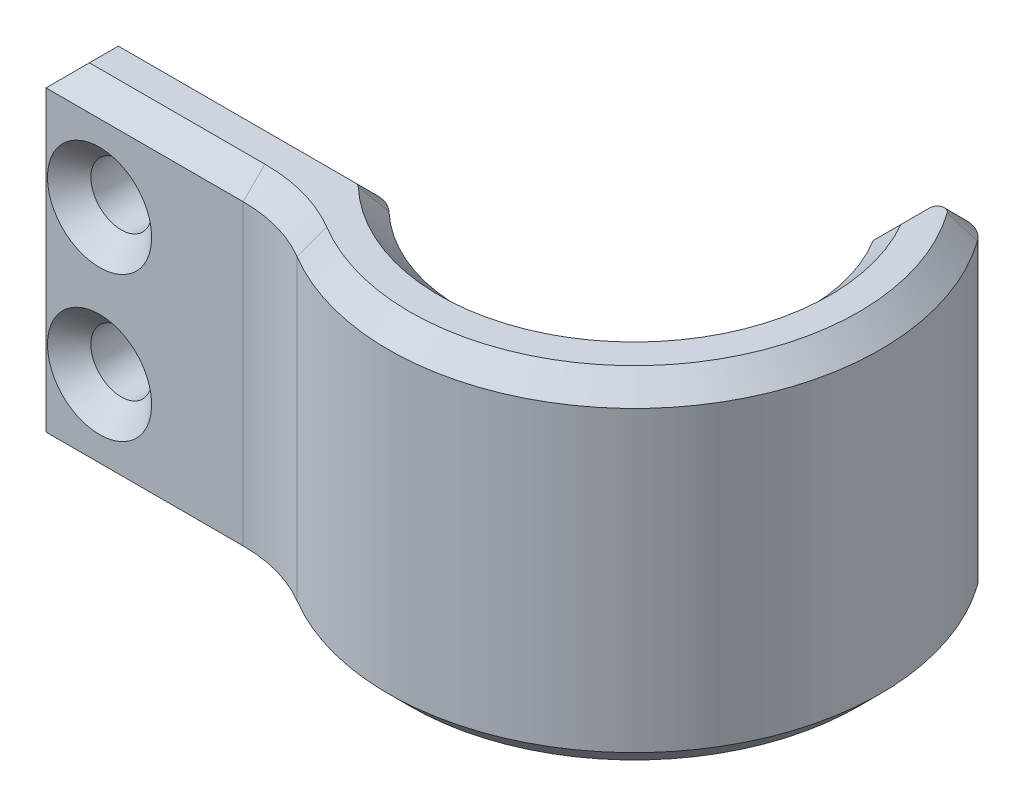
SolidWorks part; units mm, degrees
ref_plane "Alzado" through (0, 0, 0) normal (0, 0, 1) x (1, 0, 0)
ref_plane "Planta" through (0, 0, 0) normal (0, 1, 0) x (1, 0, 0)
ref_plane "Vista lateral" through (0, 0, 0) normal (1, 0, 0) x (0, 0, -1)
sketch "Croquis1" plane through (0, 0, 0) normal (0, 0, 1) x (1, 0, 0)
  line L0 (0, -11.8) -> (34.55, -11.8) construction
  line L1 (20.55, -11.8) -> (36.05, -11.8)
  line L2 (20.55, -11.8) -> (20.55, 11.8)
  line L3 (20.55, 11.8) -> (36.05, 11.8)
  line L4 (36.05, -11.8) -> (36.05, 11.8)
  line L5 (20.45, -10.3) -> (20.45, 10.3) construction
  line L6 (36.05, 13.3) -> (36.05, -13.3) construction
  line L7 (34.55, 11.8) -> (0, 11.8) construction
  circle A0 centre (24.25, -5) radius 2.1
  circle A1 centre (24.25, 5) radius 2.1
  circle A2 centre (24.25, -5) radius 2.1 construction
  dimension "D1" = 0.1
extrude "Saliente-Extruir1" add sketch "Croquis1" along normal blind 5
sketch "Croquis2" plane through (0, 0, 0) normal (0, 1, 0) x (1, 0, 0)
  line L0 (36.05, 12.9255) -> (36.05, 3.4021)
  line L1 (36.05, 1.5) -> (36.05, 47.6) construction
  line L2 (36.05, -5) -> (37.2929, -5)
  line L3 (36.05, 0) -> (39.255, 0)
  line L4 (58.2685, 21.7499) -> (58.2685, 14.4552)
  line L5 (36.05, 0) -> (36.05, -5)
  circle A0 centre (48.05, 8.1638) radius 12 construction
  arc A1 (37.2929, -5) -> (58.2685, 21.7499) centre (48.05, 8.1638) ccw
  arc A2 (39.255, 0) -> (58.2685, 14.4552) centre (48.05, 8.1638) ccw
  point P6 (36.05, 8.1638)
  dimension "D1" = 24
  dimension "D3" = 5
  dimension "D2" = 0
extrude "Saliente-Extruir2" add sketch "Croquis2" against normal up to surface and the other way up to surface contours A2 L3 L5 L2 A1 L4 region at (36.4715, 0, 2.5) up to face at (28.3, -11.8, 2.5) other way up to face at (28.3, 11.8, 2.5)
fillet "Redondeo1" radius 2 2 edges at (39.255, 0, 0) (58.2685, 0, -21.7499)
fillet "Redondeo2" radius 10 1 edges at (37.2929, 0, 5)
chamfer "Chaflán1" distance 1.5 angle 45 18 edges at (58.2685, 11.8, -15.66) (59.6595, 11.8, -18.7699) (60.5374, 11.8, 3.3716) (36.8431, 11.8, 5.3617) (27.3639, 11.8, 5) (20.55, 11.8, 2.5) (29.486, 11.8, 0) (39.1623, 11.8, 0.1421) (55.6158, 11.8, 1.1507) (20.55, -11.8, 2.5) (27.3639, -11.8, 5) (36.8431, -11.8, 5.3617) (60.5374, -11.8, 3.3716) (59.6595, -11.8, -18.7699) (58.2685, -11.8, -15.66) (55.6158, -11.8, 1.1507) (39.1623, -11.8, 0.1421) (29.486, -11.8, 0)
chamfer "Chaflán2" distance 1.5 angle 45 2 edges at (26.35, 5, 5) (26.35, -5, 5)
